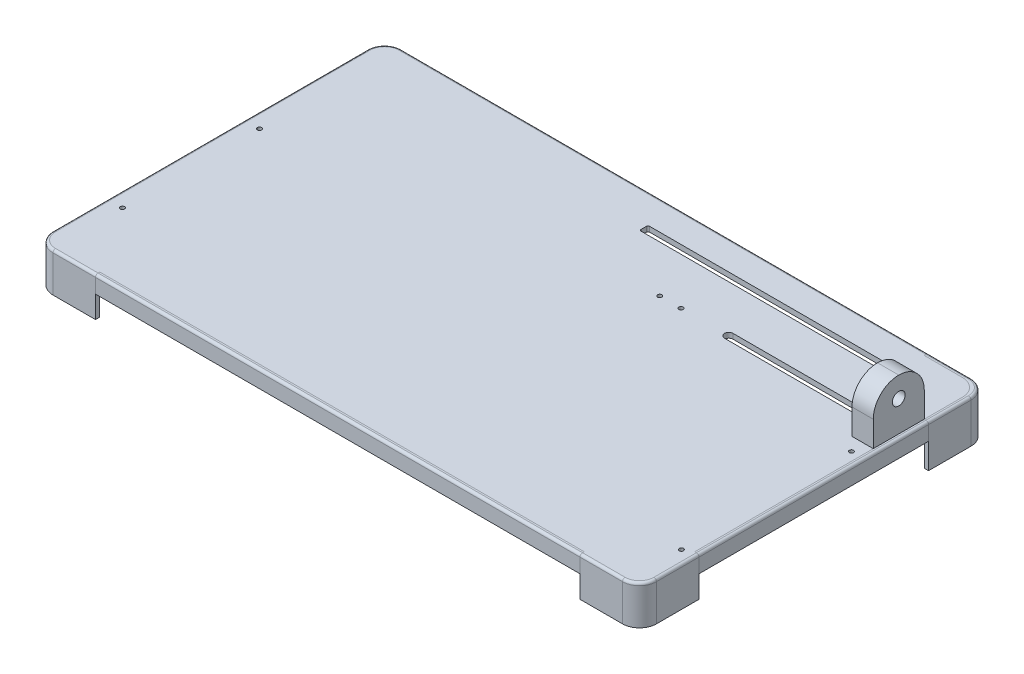
SolidWorks part; units mm, degrees
material "Cast Alloy Steel"
ref_plane "Front Plane" through (0, 0, 0) normal (0, 0, 1) x (1, 0, 0)
ref_plane "Top Plane" through (0, 0, 0) normal (0, 1, 0) x (1, 0, 0)
ref_plane "Right Plane" through (0, 0, 0) normal (1, 0, 0) x (0, 0, -1)
sketch "Sketch1" plane through (0, 0, 0) normal (0, 1, 0) x (1, 0, 0)
  line L1 (-350, 200) -> (350, 200)
  line L2 (-350, 200) -> (-350, -200)
  line L3 (-350, -200) -> (350, -200)
  line L4 (350, 200) -> (350, -200)
  dimension "D1" = 700
  dimension "D2" = 400
  dimension "D3" = 350
  dimension "D4" = 200
extrude "Boss-Extrude1" add sketch "Sketch1" along normal blind 6
sketch "Sketch3" plane through (0, 6, 0) normal (0, 1, 0) x (-1, 0, 0)
  line L0 (-350, -200) -> (350, -200) construction
  line L1 (10, -170) -> (-300, -170)
  line L2 (10, -170) -> (10, -160)
  line L3 (10, -160) -> (-300, -160)
  line L4 (-300, -170) -> (-300, -160)
  line L5 (-350, 200) -> (-350, -200) construction
  dimension "D1" = 310
  dimension "D2" = 10
  dimension "D3" = 30
  dimension "D4" = 50
extrude "Cut-Extrude1" cut sketch "Sketch3" against normal blind 26
fillet "Fillet1" radius 2 4 edges at (300, 3, -160) (300, 3, -170) (-10, 3, -170) (-10, 3, -160)
sketch "Sketch4" plane through (0, 6, 0) normal (0, 1, 0) x (-1, 0, 0)
  line L0 (-145, -200) -> (-145, -120.068) construction
  line L1 (-350, -200) -> (350, -200) construction
  line L2 (10, -168) -> (10, -162) construction
  dimension "D1" = 155
sketch "Sketch5" plane through (0, 6, 0) normal (0, 1, 0) x (-1, 0, 0)
  line L0 (10, -165) -> (-330.0789, -165) construction
  line L1 (10, -168) -> (10, -162) construction
ref_plane "Plane1" through (0, 0, -165) normal (0, 0, 1) x (1, 0, 0)
fillet "Fillet2" radius 20 4 edges at (350, 3, -200) (350, 3, 200) (-350, 3, -200) (-350, 3, 200)
sketch "Sketch8" plane through (0, 0, 0) normal (0, -1, 0) x (1, 0, 0)
  line L0 (-355, 135) -> (-355, 185)
  line L1 (-335, 205) -> (-285, 205)
  line L2 (-350, -180) -> (-350, 180) construction
  line L3 (-330, 200) -> (330, 200) construction
  line L4 (-355, 135) -> (-350, 135)
  line L5 (-350, 135) -> (-350, 180)
  line L6 (-330, 200) -> (-285, 200)
  line L7 (-285, 200) -> (-285, 205)
  arc A0 (-335, 205) -> (-355, 185) centre (-335, 185) ccw
  arc A1 (-350, 180) -> (-330, 200) centre (-330, 180) cw
  dimension "D3" = 20
  dimension "D1" = 5
  dimension "D2" = 5
  dimension "D4" = 50
  dimension "D5" = 50
extrude "Boss-Extrude2" add sketch "Sketch8" along normal blind 40 and the other way blind 6 separate body
mirror "Mirror3" about plane through (0, 0, 0) normal (0, 0, 1) of "Boss-Extrude2"
mirror "Mirror6" about plane through (0, 0, 0) normal (1, 0, 0) of "Boss-Extrude2"
sketch "Sketch9" plane through (0, 6, 0) normal (0, 1, 0) x (-1, 0, 0)
  line L0 (-355, -135) -> (-355, -185)
  line L1 (-285, -205) -> (-335, -205)
  line L2 (-330, -200) -> (285, -200) construction
  line L3 (-350, 135) -> (-350, -180) construction
  line L4 (-285, -205) -> (-285, -200)
  line L5 (-355, -135) -> (-350, -135)
  line L6 (-285, -200) -> (-330, -200)
  line L7 (-350, -180) -> (-350, -135)
  arc A0 (-355, -185) -> (-335, -205) centre (-335, -185) ccw
  arc A1 (-350, -180) -> (-330, -200) centre (-330, -180) ccw construction
  arc A2 (-330, -200) -> (-350, -180) centre (-330, -180) cw
  point P9 (-355, -205)
  dimension "D5" = 20
  dimension "D1" = 5
  dimension "D2" = 5
  dimension "D3" = 70
  dimension "D4" = 70
extrude "Boss-Extrude3" add sketch "Sketch9" against normal blind 50 separate body
sketch "Sketch10" plane through (0, 6, 0) normal (0, 1, 0) x (-1, 0, 0)
  line L1 (285, 205) -> (-285, 205)
  line L2 (285, 205) -> (285, 200)
  line L3 (285, 200) -> (-285, 200)
  line L4 (-285, 205) -> (-285, 200)
extrude "Boss-Extrude4" add sketch "Sketch10" against normal blind 20 separate body
sketch "Sketch11" plane through (0, 6, 0) normal (0, 1, 0) x (-1, 0, 0)
  line L1 (-350, -135) -> (-355, -135)
  line L2 (-350, -135) -> (-350, 135)
  line L3 (-350, 135) -> (-355, 135)
  line L4 (-355, -135) -> (-355, 135)
extrude "Boss-Extrude5" add sketch "Sketch11" against normal blind 20 separate body
pattern_linear "LPattern1" count 1 spacing 705 along (-1, 0, 0) count 2 spacing 405 along (0, 0, -1) of "Boss-Extrude4"
pattern_linear "LPattern2" count 2 spacing 705 along (-1, 0, 0) of "Boss-Extrude5"
fillet "Fillet3" radius 3 1 edges at (0, 6, 205)
fillet "Fillet4" radius 3 1 edges at (355, 6, 0)
fillet "Fillet5" radius 3 3 edges at (355, 6, 160) (349.1421, 6, 199.1421) (310, 6, 205)
fillet "Fillet6" radius 3 3 edges at (355, 6, -160) (310, 6, -205) (349.1421, 6, -199.1421)
fillet "Fillet7" radius 3 5 edges at (-310, 6, 205) (-349.1421, 6, 199.1421) (-355, 6, 0) (-349.1421, 6, -199.1421) (-25, 6, -205)
hole_wizard "Ø5.0 (5) Diameter Hole1" positions "Sketch13" profile "Sketch12" hole size "Ø5.0" standard "ISO"
sketch "Sketch13" plane through (0, 6, 0) normal (0, 1, 0) x (-1, 0, 0)
  line L0 (8, -160) -> (-298, -160) construction
  point P0 (-68.81, -105)
  point P1 (-93.81, -105)
  dimension "D1" = 25
  dimension "D2" = 78.81
  dimension "D3" = 55
sketch "Sketch12" plane through (68.81, 6, -105) normal (1, 0, 0) x (0, 0, 1)
  line L0 (0, 0) -> (0, 12.5022)
  line L1 (0, 12.5022) -> (2.5, 11)
  line L2 (2.5, 11) -> (2.5, 0)
  line L5 (2.5, 0) -> (0, 0)
  line L10 (0, 12.5022) -> (-2.5, 11) construction
  line L11 (0, -6.35) -> (0, 107.95) construction
  dimension "Hole Dia." = 5
  dimension "Hole Depth" = 11
  dimension "Drill Angle" = 118
cosmetic thread "Cosmetic Thread1" parameters "D2"=6
sketch "Sketch14" plane through (0, 6, 0) normal (0, 1, 0) x (-1, 0, 0)
  line L0 (-71.31, -105) -> (-371.5443, -105) construction
  line L1 (-350, 135) -> (-350, -180) construction
  line L2 (-325, -135) -> (-350, -135)
  line L3 (-325, -135) -> (-325, -75)
  line L4 (-325, -75) -> (-350, -75)
  line L5 (-350, -135) -> (-350, -75)
  circle A0 centre (-68.81, -105) radius 2.5 construction
  dimension "D1" = 60
  dimension "D2" = 25
  dimension "D3" = 30
  dimension "D4" = 0
extrude "Boss-Extrude6" add sketch "Sketch14" along normal blind 60 separate body
fillet "Fillet8" radius 30 2 edges at (337.5, 66, -135) (337.5, 66, -75)
sketch "Sketch15" plane through (0, 6, 0) normal (0, 1, 0) x (-1, 0, 0)
  line L0 (-96.31, -105) -> (-376.9619, -105) construction
  line L2 (-150, -110) -> (-300, -110)
  line L4 (-150, -100) -> (-300, -100)
  circle A0 centre (-93.81, -105) radius 2.5 construction
  arc A1 (-150, -110) -> (-150, -100) centre (-150, -105) ccw
  arc A2 (-300, -110) -> (-300, -100) centre (-300, -105) cw
  dimension "D2" = 150
  dimension "D3" = 5
  dimension "D4" = 10
extrude "Cut-Extrude2" cut sketch "Sketch15" against normal blind 60
sketch "Sketch16" plane through (350, 0, 0) normal (1, 0, 0) x (0, 0, -1)
  line L0 (75, 36) -> (75, 6) construction
  line L1 (-135, 6) -> (180, 6) construction
  circle A0 centre (105, 42) radius 7.5
  dimension "D1" = 15
  dimension "D2" = 30
  dimension "D3" = 36
extrude "Cut-Extrude3" cut sketch "Sketch16" against normal blind 40
cosmetic thread "Cosmetic Thread2" parameters "D2"=18
hole_wizard "Ø5.0 (5) Diameter Hole2" positions "Sketch18" profile "Sketch17" hole size "Ø5.0" standard "Ansi Metric"
sketch "Sketch18" plane through (0, 6, 0) normal (0, 1, 0) x (-1, 0, 0)
  line L0 (-352, 185) -> (-352, 135) construction
  line L1 (-285, 202) -> (-335, 202) construction
  point P0 (-340, 140.67)
  point P1 (-340, -59.33)
  dimension "D1" = 12
  dimension "D2" = 61.33
  dimension "D3" = 200
  dimension "D4" = 12
sketch "Sketch17" plane through (340, 6, 140.67) normal (1, 0, 0) x (0, 0, 1)
  line L0 (0, 0) -> (0, 12.5022)
  line L1 (0, 12.5022) -> (2.5, 11)
  line L2 (2.5, 11) -> (2.5, 0)
  line L5 (2.5, 0) -> (0, 0)
  line L10 (0, 12.5022) -> (-2.5, 11) construction
  line L11 (0, -6.35) -> (0, 107.95) construction
  dimension "Hole Dia." = 5
  dimension "Hole Depth" = 11
  dimension "Drill Angle" = 118
cosmetic thread "Cosmetic Thread3" parameters "D2"=6
cosmetic thread "Cosmetic Thread4" parameters "D2"=6
hole_wizard "Ø5.0 (5) Diameter Hole3" positions "Sketch20" profile "Sketch19" hole size "Ø5.0" standard "Ansi Metric"
sketch "Sketch20" plane through (0, 6, 0) normal (0, 1, 0) x (-1, 0, 0)
  line L1 (-285, -202) -> (335, -202) construction
  line L2 (352, -185) -> (352, 185) construction
  point P0 (337, -40)
  point P1 (337, 121.29)
  dimension "D1" = 161.29
  dimension "D2" = 162
  dimension "D3" = 15
  dimension "D4" = 15
sketch "Sketch19" plane through (-337, 6, -40) normal (1, 0, 0) x (0, 0, 1)
  line L0 (0, 0) -> (0, 12.5022)
  line L1 (0, 12.5022) -> (2.5, 11)
  line L2 (2.5, 11) -> (2.5, 0)
  line L5 (2.5, 0) -> (0, 0)
  line L10 (0, 12.5022) -> (-2.5, 11) construction
  line L11 (0, -6.35) -> (0, 107.95) construction
  dimension "Hole Dia." = 5
  dimension "Hole Depth" = 11
  dimension "Drill Angle" = 118
cosmetic thread "Cosmetic Thread5" parameters "D2"=6
cosmetic thread "Cosmetic Thread6" parameters "D2"=6
